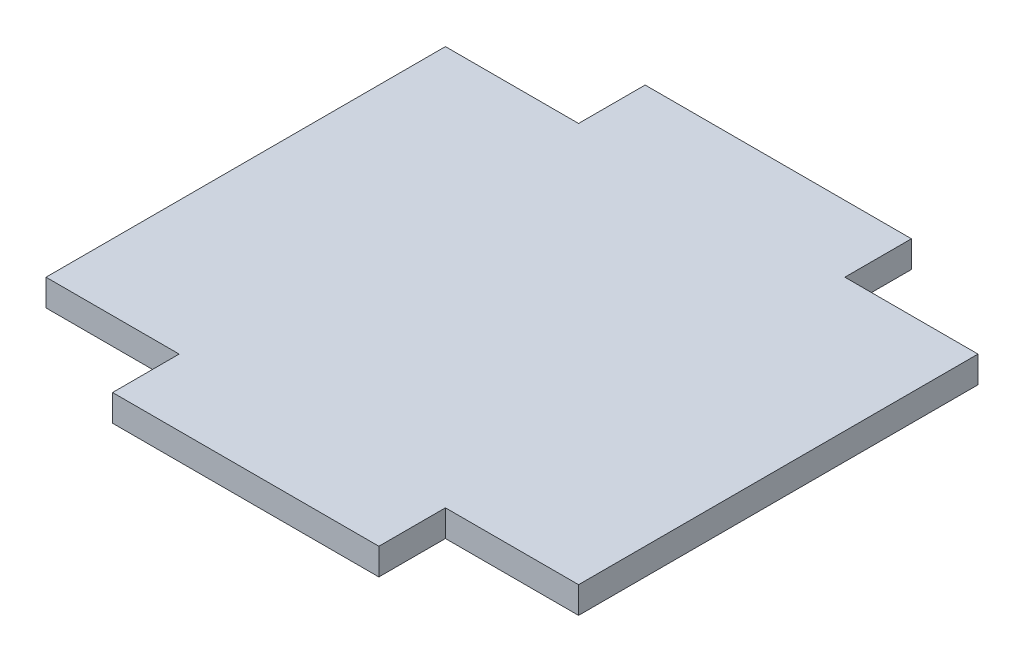
SolidWorks part; units mm, degrees
ref_plane "Alzado" through (0, 0, 0) normal (0, 0, 1) x (1, 0, 0)
ref_plane "Planta" through (0, 0, 0) normal (0, 1, 0) x (1, 0, 0)
ref_plane "Vista lateral" through (0, 0, 0) normal (1, 0, 0) x (0, 0, -1)
sketch "Croquis2" plane through (0, 0, 0) normal (0, 0, 1) x (1, 0, 0)
  line L0 (-0.5, 0.05) -> (0.5, 0.05)
  line L1 (-0.5, 0.05) -> (-0.5, -0.05)
  line L2 (-0.5, -0.05) -> (0.5, -0.05)
  line L3 (0.5, -0.05) -> (0.5, 0.05)
  point P0 (0.5, 0)
  point P5 (0, 0.05)
  dimension "D2" = 0.1
  dimension "D3" = 1
extrude "Saliente-Extruir2" add sketch "Croquis2" along normal blind 1 and the other way blind 1
sketch "Croquis3" plane through (0, 0, 0) normal (1, 0, 0) x (0, 0, -1)
  line L0 (1, 0.05) -> (-1, 0.05) construction
  line L1 (-0.75, 0.05) -> (0.75, 0.05)
  line L2 (-0.75, 0.05) -> (-0.75, -0.05)
  line L3 (-0.75, -0.05) -> (0.75, -0.05)
  line L4 (0.75, 0.05) -> (0.75, -0.05)
  line L5 (1, -0.05) -> (-1, -0.05) construction
  point P8 (0, 0.05)
  dimension "D1" = 1.5
extrude "Saliente-Extruir3" add sketch "Croquis3" along normal blind 1 and the other way blind 1
